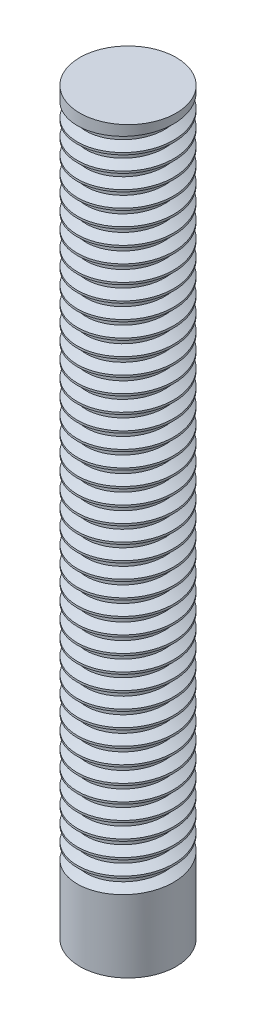
SolidWorks part; units mm, degrees
ref_plane "Front Plane" through (0, 0, 0) normal (0, 0, 1) x (1, 0, 0)
ref_plane "Top Plane" through (0, 0, 0) normal (0, 1, 0) x (1, 0, 0)
ref_plane "Right Plane" through (0, 0, 0) normal (1, 0, 0) x (0, 0, -1)
sketch "Sketch1" plane through (0, 0, 0) normal (0, 1, 0) x (1, 0, 0)
  circle A0 centre (0, 0) radius 3
extrude "Boss-Extrude1" add sketch "Sketch1" along normal blind 46
thread "Thread1" pitch 1 method cut profile "Thread Profile1" start angle 0, offset 0, length 0, pitch 1, diameter 6
ref_plane "Plane1" through (-3, 46, 0) normal (0, 0, 1) x (-1, 0, 0)
sketch "Thread Profile1" plane through (-3, 46, 0) normal (0, 0, 1) x (-1, 0, 0)
  line L0 (0, 0) -> (0, 1) construction
  line L11 (0, 0) -> (0, 0.875)
  line L12 (0, 0.875) -> (-0.5413, 0.5625)
  line L13 (-0.5413, 0.5625) -> (-0.5413, 0.3125)
  line L15 (-0.5413, 0.3125) -> (0, 0)
  line L17 (-0.5413, 0.4375) -> (0, 0.4375) construction
  point P2 (0, 0)
  dimension "Pitch" = 1
  dimension "Profile_Angle" = 60
  dimension "Profile_Land" = 0.25
  dimension "Profile_Height" = 0.5413
